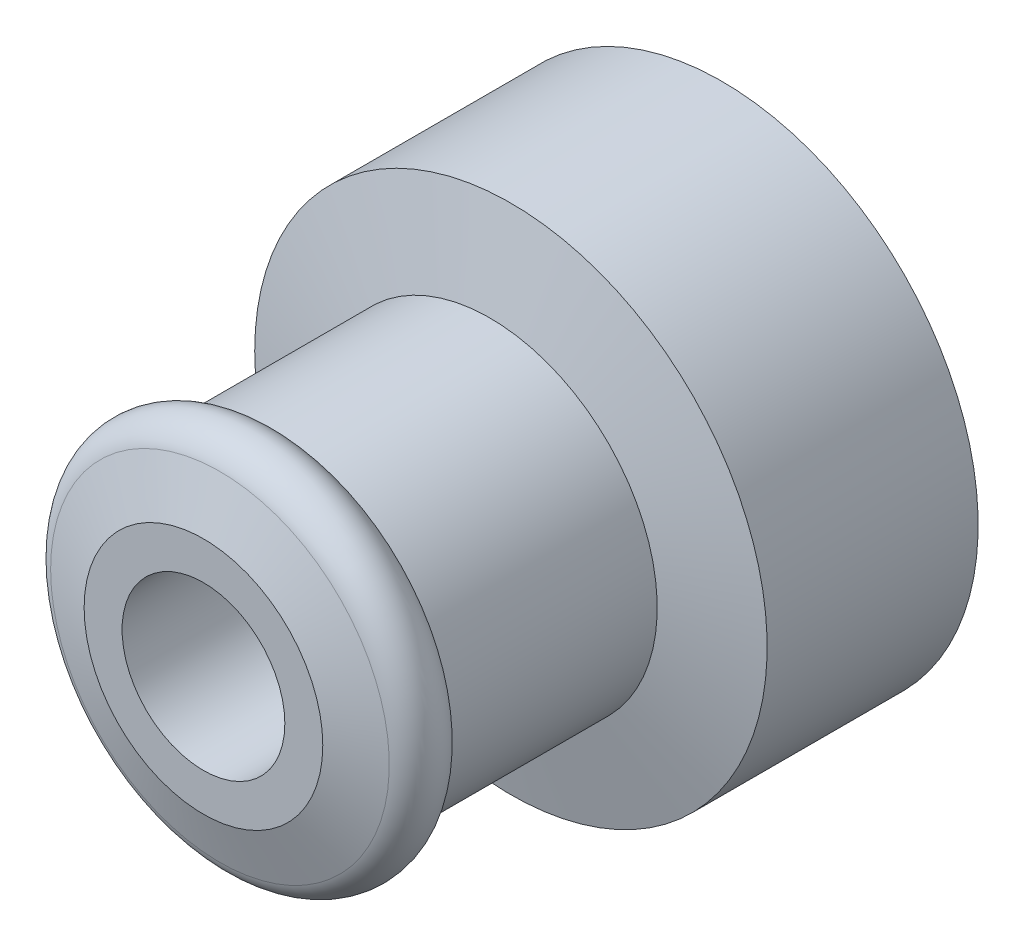
SolidWorks part; units mm, degrees
ref_plane "Сверху" through (0, 0, 0) normal (0, 0, 1) x (1, 0, 0)
ref_plane "Справа" through (0, 0, 0) normal (0, 1, 0) x (1, 0, 0)
ref_plane "Спереди" through (0, 0, 0) normal (1, 0, 0) x (0, 0, -1)
sketch "Эскиз1" plane through (0, 0, 0) normal (0, 0, 1) x (1, 0, 0)
  line L0 (0, 0) -> (0, 8.5)
  line L1 (7, 8.5) -> (0, 8.5)
  line L2 (17.2, 3.9586) -> (17.2, 0)
  line L3 (7, 8.5) -> (7.6974, 5.55)
  line L4 (7.6974, 5.55) -> (14.6974, 5.55)
  line L7 (17.2, 3.9586) -> (16.6529, 5.617)
  line L11 (0, 0) -> (17.2, 0)
  arc A0 (16.6529, 5.617) -> (14.6974, 5.55) centre (15.685, 5.2977) ccw
  dimension "D2" = 7
  dimension "D1" = 17.2
  dimension "D3" = 7
  dimension "D6" = 5.55
revolve "Body" add sketch "Эскиз1" angle 360 about L11 region at (7.732, 3.5741, 0)
sketch "Эскиз2" plane through (17.2, 0, 0) normal (1, 0, 0) x (0, 0, -1)
  circle A0 centre (0, 0) radius 2.7
  dimension "D1" = 5.4
extrude "Bore" cut sketch "Эскиз2" against normal through all from offset 1
sketch "Эскиз4" plane through (0, 0, 0) normal (0, 0, 1) x (1, 0, 0)
  line L0 (1.8257, 2.8062) -> (-1.1125, 2.8062)
  line L1 (6.7403, 0) -> (5.1201, 2.8062)
  line L2 (5.1201, 2.8062) -> (1.8257, 2.8062)
  line L5 (1.8257, -2.8062) -> (5.1201, -2.8062)
  line L6 (5.1201, -2.8062) -> (6.7403, 0)
  line L7 (-1.1125, 2.8062) -> (-1.1125, -2.8062)
  line L8 (-1.1125, -2.8062) -> (1.8257, -2.8062)
  line L10 (1.0698, 1.4031) -> (0.2326, -0.0469) [skipped]
  line L11 (0.2326, 0.0469) -> (1.0698, -1.4031) [skipped]
  circle A0 centre (3.5, 0) radius 1.7
  dimension "D1" = 3.4
  dimension "D2" = 3.5
extrude "Fix" cut sketch "Эскиз4" along normal through all from offset 3.2 contours A0 region at (3.5, 0, 0)
extrude "Вырез-Вытянуть1" cut sketch "Эскиз4<3>" along normal blind 2.8 from offset 2.5 contours L7 L8 L5 L6 L1 L2 L0 A0 | A0 region at (3.4729, 2.7096, 0) region at (3.5, 0, 0)
sketch "Эскиз4<3>" plane through (0, 0, 0) normal (0, 0, 1) x (1, 0, 0) same geometry as "Эскиз4"
move or copy body "Тело-Переместить/Копировать1" bodies to move or copy 115 copy no rotation origin (8, 0, 0) rotation axis (0, -1, 0) rotation angle 90
fillet "Скругление1" radius 0.15 2 edges at (5.5, -1.0198, -4.9243) (5.5, 1.0198, -4.9243)
